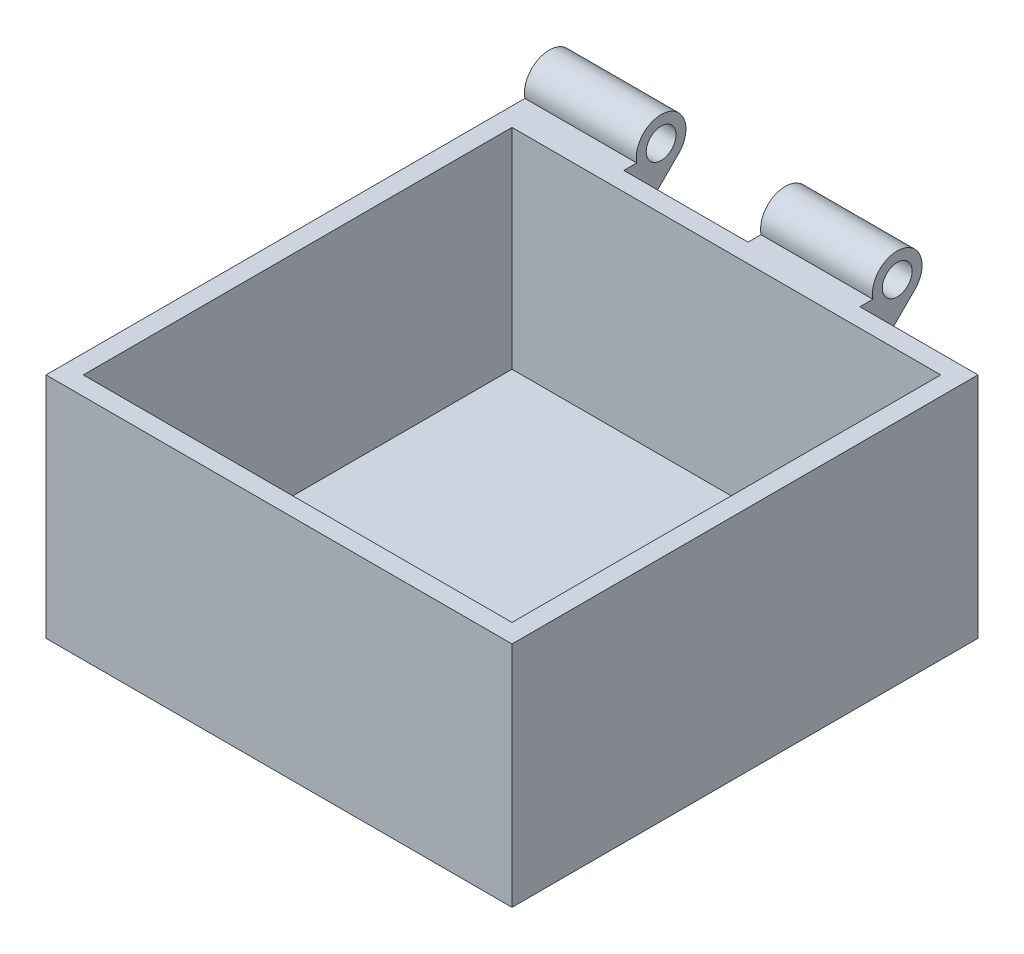
SolidWorks part; units mm, degrees
ref_plane "Front Plane" through (0, 0, 0) normal (0, 0, 1) x (1, 0, 0)
ref_plane "Top Plane" through (0, 0, 0) normal (0, 1, 0) x (1, 0, 0)
ref_plane "Right Plane" through (0, 0, 0) normal (1, 0, 0) x (0, 0, -1)
sketch "Sketch1" plane through (0, 0, 0) normal (0, 1, 0) x (1, 0, 0)
  line L1 (-47.625, 47.625) -> (47.625, 47.625)
  line L2 (-47.625, 47.625) -> (-47.625, -47.625)
  line L3 (-47.625, -47.625) -> (47.625, -47.625)
  line L4 (47.625, 47.625) -> (47.625, -47.625)
  point P4 (0, 47.625)
  point P6 (47.625, 0)
  dimension "D1" = 95.25
  dimension "D2" = 95.25
extrude "Boss-Extrude1" add sketch "Sketch1" along normal blind 47.625
shell "Shell1" thickness 3.81 removed face at (0, 47.625, 0)
sketch "Sketch2" plane through (-47.625, 0, 0) normal (-1, 0, 0) x (0, 0, 1)
  line L0 (-58.8371, 44.0329) -> (-47.625, 32.8208)
  line L1 (-47.625, 47.625) -> (-47.625, 0) construction
  line L2 (-47.625, 47.625) -> (-50.165, 47.625)
  line L3 (-50.2644, 46.625) -> (47.625, 46.625)
  line L4 (47.625, 47.625) -> (47.625, 0) construction
  line L5 (-47.625, 47.625) -> (47.625, 47.625) construction
  arc A0 (-50.165, 47.625) -> (-58.8371, 44.0329) centre (-55.245, 47.625) ccw
  circle A1 centre (-55.245, 47.625) radius 3.048
  arc A2 (-50.165, 47.625) -> (-50.2644, 46.625) centre (-55.245, 47.625) cw
  line M3 (47.625, 0) -> (47.625, 47.625)
  line M4 (47.625, 47.625) -> (-47.625, 47.625)
  line M5 (-47.625, 47.625) -> (-47.625, 0)
  dimension "D1" = 7.62
  dimension "D2" = 45
  dimension "D3" = 10.16
  dimension "D4" = 6.096
  dimension "D5" = 1
extrude "Boss-Extrude2" add sketch "Sketch2" against normal blind 22.86 contours L2 A0 L0 A1 M5 region at (-47.625, 43.737, -52.7066)
sketch "Sketch5" plane through (47.625, 0, 0) normal (1, 0, 0) x (0, 0, -1)
  line L3 (50.2644, 46.625) -> (47.625, 46.625)
  line L4 (47.625, 46.625) -> (47.625, 32.8208)
  line L5 (47.625, 32.8208) -> (58.8371, 44.0329)
  line L7 (47.625, 46.625) -> (47.625, 32.8208)
  line L8 (47.625, 32.8208) -> (58.8371, 44.0329)
  line L9 (50.2644, 46.625) -> (47.625, 46.625)
  circle A1 centre (55.245, 47.625) radius 3.048
  circle A2 centre (55.245, 47.625) radius 3.048
  arc A3 (58.8371, 44.0329) -> (50.2644, 46.625) centre (55.245, 47.625) ccw
  arc A4 (58.8371, 44.0329) -> (50.2644, 46.625) centre (55.245, 47.625) ccw
  dimension "D1" = 0
  dimension "D2" = 0
extrude "Boss-Extrude3" add sketch "Sketch5" against normal blind 22.86 from offset 24.13 offset against normal yes
extrude "Cut-Extrude1" cut sketch "Sketch2<3>" against normal through all contours L3 M5 M3 M4 region at (-47.625, 47.125, 0)
sketch "Sketch2<3>" plane through (-47.625, 0, 0) normal (-1, 0, 0) x (0, 0, 1) same geometry as "Sketch2"
